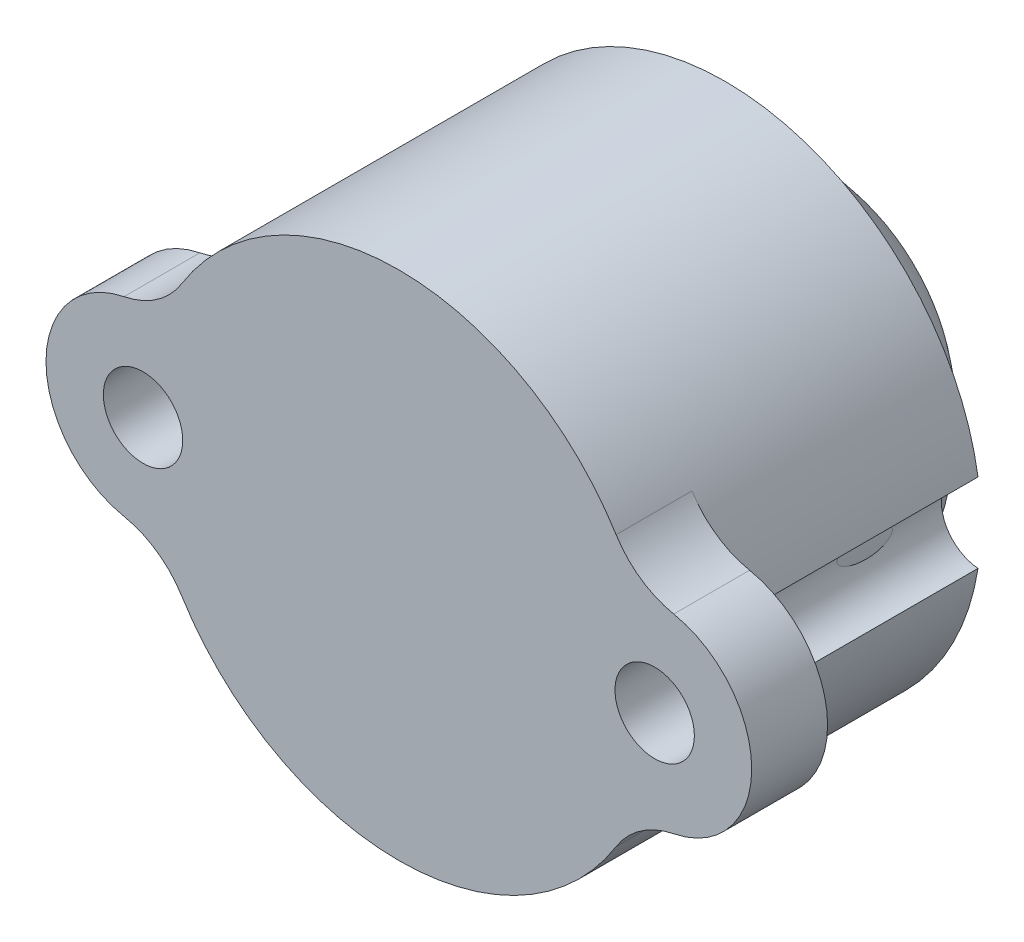
SolidWorks part; units mm, degrees
material "Nickel"
ref_plane "Plan de face" through (0, 0, 0) normal (0, 0, 1) x (1, 0, 0)
ref_plane "Plan de dessus" through (0, 0, 0) normal (0, 1, 0) x (1, 0, 0)
ref_plane "Plan de droite" through (0, 0, 0) normal (1, 0, 0) x (0, 0, -1)
sketch "Esquisse1" plane through (0, 0, 0) normal (0, 0, 1) x (1, 0, 0)
  circle A0 centre (0, 0) radius 7.366
  dimension "D1" = 14.732
extrude "Boss.-Extru.1" add sketch "Esquisse1" along normal blind 9.398
sketch "Esquisse2" plane through (0, 0, 9.398) normal (0, 0, 1) x (1, 0, 0)
  line L0 (-7.366, 0) -> (7.366, 0) construction
  line L1 (-7.366, 2.794) -> (7.366, 2.794)
  line L2 (-7.366, -2.794) -> (7.366, -2.794)
  line L3 (-10.16, 0) -> (10.16, 0)
  arc A0 (-7.366, 2.794) -> (-7.366, -2.794) centre (-7.366, 0) ccw
  arc A1 (7.366, -2.794) -> (7.366, 2.794) centre (7.366, 0) ccw
  point P2 (0, 0)
  point P7 (0, 0)
  circle M3 centre (0, 0) radius 7.366
  dimension "D2" = 20.32
  dimension "D1" = 14.732
extrude "Boss.-Extru.2" add sketch "Esquisse2" against normal blind 2.1844 contours L3 A1 L1 M3 | L2 A1 L3 M3 | L3 A0 L2 M3 | L1 A0 L3 M3 region at (-8.4491, 1.2554, 9.398) region at (-8.4491, -1.2554, 9.398) region at (8.4491, 1.2554, 9.398) region at (8.4491, -1.2554, 9.398)
fillet "Congé1" radius 2.54 4 edges at (6.8155, 2.794, 8.3058) (6.8155, -2.794, 8.3058) (-6.8155, -2.794, 8.3058) (-6.8155, 2.794, 8.3058)
sketch "Esquisse3" plane through (0, 0, 9.398) normal (0, 0, 1) x (1, 0, 0)
  line L0 (-7.366, 0) -> (7.366, 0)
  circle A0 centre (-7.366, 0) radius 1.143
  circle A1 centre (7.366, 0) radius 1.143
  point P4 (0, 0)
  dimension "D2" = 2.286
  dimension "D3" = 2.286
  dimension "D1" = 14.732
extrude "Enlèv. mat.-Extru.2" cut sketch "Esquisse3" against normal through all contours A0 | A1 region at (-8.4767, 0, 9.398)
sketch "Esquisse4" plane through (0, 0, 0) normal (1, 0, 0) x (0, 0, -1)
  line L2 (-7.0373, 0) -> (7.1163, 0) construction
  line L3 (-8.4836, 0) -> (4.064, 0)
  line L4 (-9.398, -3.8892) -> (-9.398, -7.366) construction
  arc A0 (4.064, 0) -> (-8.4836, 0) centre (-2.2098, 0) ccw
  dimension "D1" = 12.5476
  dimension "D2" = 13.462
revolve "Révolution4" add sketch "Esquisse4" angle 360 about L2
